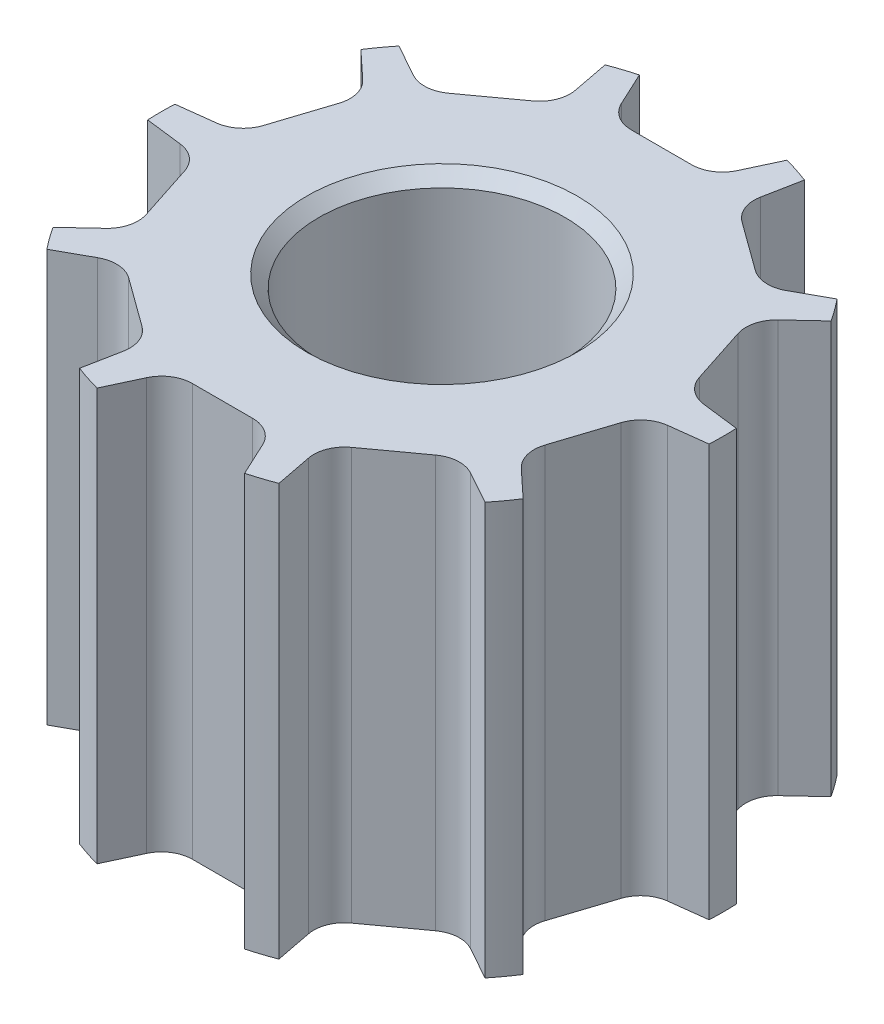
SolidWorks part; units mm, degrees
material "6061-T6 (SS)"
ref_plane "Ebene vorne" through (0, 0, 0) normal (0, 0, 1) x (1, 0, 0)
ref_plane "Ebene oben" through (0, 0, 0) normal (0, 1, 0) x (1, 0, 0)
ref_plane "Ebene rechts" through (0, 0, 0) normal (1, 0, 0) x (0, 0, -1)
ref_axis "Achse1" through (0, -12.75, 0) along (0, 1, 0)
sketch "Skizze1" plane through (0, 0, 0) normal (0, 1, 0) x (1, 0, 0)
  circle A0 centre (0, 0) radius 4.57
  circle A1 centre (0, 0) radius 2
  dimension "D1" = 9.14
  dimension "D2" = 4
extrude "Aufsatz-Linear austragen1" add sketch "Skizze1" along normal blind 6.7
sketch "Skizze12" plane through (0, 6.7, 0) normal (0, 1, 0) x (1, 0, 0)
  line L0 (0, 9.2022) -> (0, -8.7185) construction
  line L1 (-8.4713, 0) -> (7.9602, 0) construction
  line L2 (-1.2, 4.4096) -> (-0.8085, 3.57)
  line L3 (1.2, 4.4096) -> (0.8085, 3.57)
  line L4 (-2.8195, 3.57) -> (2.5735, 3.57) construction
  line L5 (-2.9704, 4.57) -> (2.868, 4.57) construction
  line L6 (-0.8085, 3.57) -> (0.8085, 3.57)
  circle A1 centre (0, 0) radius 4.57 construction
  circle A2 centre (0, 0) radius 4.57 construction
  arc A4 (-1.2, 4.4096) -> (1.2, 4.4096) centre (0, 0) cw
  dimension "D1" = 1
  dimension "D5" = 1.6169
  dimension "D6" = 9.14
  dimension "D2" = 2.4
  dimension "D3" = 50
  dimension "D4" = 3.57
extrude "Schnitt-Linear austragen1" cut sketch "Skizze12" against normal through all
fillet "Verrundung1" radius 0.5 2 edges at (0.8085, 3.35, -3.57) (-0.8085, 3.35, -3.57)
pattern_circular "Kreismuster1" count 10 over 360 about axis through (0, -12.75, 0) along (0, 1, 0) of "Schnitt-Linear austragen1", "Verrundung1"
chamfer "Fase2" distance 0.2 angle 45 2 edges at (0, 6.7, 2) (0, 0, 2)
